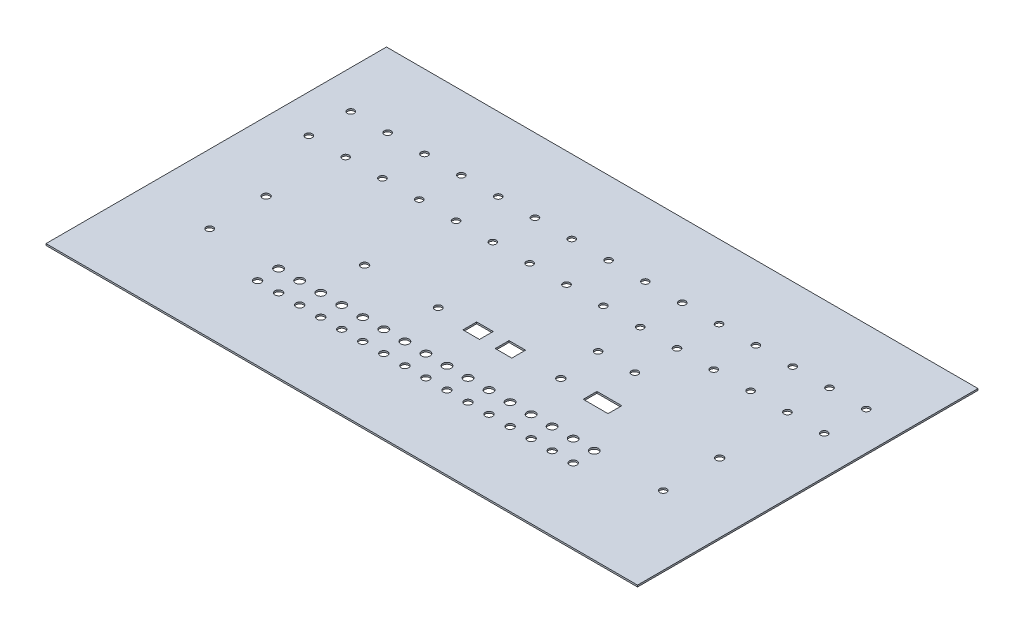
SolidWorks part; units mm, degrees
ref_plane "Front Plane" through (0, 0, 0) normal (0, 0, 1) x (1, 0, 0)
ref_plane "Top Plane" through (0, 0, 0) normal (0, 1, 0) x (1, 0, 0)
ref_plane "Right Plane" through (0, 0, 0) normal (1, 0, 0) x (0, 0, -1)
sketch "Sketch1" plane through (0, 0, 0) normal (0, 1, 0) x (1, 0, 0)
  line L1 (281.15, -161.825) -> (-281.15, -161.825)
  line L2 (281.15, -161.825) -> (281.15, 161.825)
  line L3 (281.15, 161.825) -> (-281.15, 161.825)
  line L4 (-281.15, -161.825) -> (-281.15, 161.825)
  line L5 (281.15, -161.825) -> (-281.15, 161.825) construction
  line L6 (281.15, 161.825) -> (-281.15, -161.825) construction
  point P0 (0, 0)
  dimension "D1" = 323.65
  dimension "D2" = 562.3
extrude "Boss-Extrude1" add sketch "Sketch1" along normal blind 1.5875
sketch "Sketch2" plane through (0, 1.5875, 0) normal (0, 1, 0) x (1, 0, 0)
  line L0 (-281.15, 161.825) -> (-281.15, -161.825) construction
  line L1 (281.15, 161.825) -> (-281.15, 161.825) construction
  circle A0 centre (-245, 91.825) radius 3.25
  dimension "D1" = 6.5
  dimension "D2" = 36.15
  dimension "D3" = 70
extrude "Cut-Extrude1" cut sketch "Sketch2" against normal up to next
sketch "Sketch3" plane through (0, 1.5875, 0) normal (0, 1, 0) x (1, 0, 0)
  circle A0 centre (-245, 91.825) radius 9.5
pattern_linear "LPattern1" count 15 spacing 35 along (1, 0, 0) count 2 spacing 40 along (0, 0, 1) of "Cut-Extrude1"
sketch "Sketch6" plane through (0, 1.5875, 0) normal (0, 1, 0) x (1, 0, 0)
  line L0 (-281.15, 161.825) -> (-281.15, -161.825) construction
  line L1 (-281.15, -161.825) -> (281.15, -161.825) construction
  circle A0 centre (-150, -91.825) radius 3.5
  dimension "D1" = 131.15
  dimension "D2" = 70
extrude "Cut-Extrude2" cut sketch "Sketch6" against normal up to next
pattern_linear "LPattern2" count 16 spacing 20 along (1, 0, 0) of "Cut-Extrude2"
sketch "Sketch7" plane through (0, 1.5875, 0) normal (0, 1, 0) x (1, 0, 0)
  line L0 (-281.15, 161.825) -> (-281.15, -161.825) construction
  circle A0 centre (-150, -71.825) radius 4
  circle A1 centre (-150, -91.825) radius 3.5 construction
  dimension "D1" = 131.15
  dimension "D2" = 20
extrude "Cut-Extrude3" cut sketch "Sketch7" against normal up to next
pattern_linear "LPattern3" count 16 spacing 20 along (1, 0, 0) of "Cut-Extrude3"
sketch "Sketch8" plane through (0, 1.5875, 0) normal (0, 1, 0) x (1, 0, 0)
  line L1 (-281.15, 161.825) -> (-281.15, -161.825) construction
  line L2 (-281.15, -161.825) -> (281.15, -161.825) construction
  circle A0 centre (-215.575, -71.825) radius 3.3
  dimension "D1" = 90
  dimension "D2" = 65.575
extrude "Cut-Extrude4" cut sketch "Sketch8" against normal up to next
sketch "Sketch10" plane through (0, 1.5875, 0) normal (0, 1, 0) x (1, 0, 0)
  line L0 (281.15, -161.825) -> (281.15, 161.825) construction
  line L1 (-281.15, -161.825) -> (281.15, -161.825) construction
  circle A0 centre (215.575, -71.825) radius 3.25
  dimension "D1" = 65.575
  dimension "D2" = 90
extrude "Cut-Extrude5" cut sketch "Sketch10" against normal up to next
sketch "Sketch11" plane through (0, 1.5875, 0) normal (0, 1, 0) x (1, 0, 0)
  line L0 (281.15, 161.825) -> (-281.15, 161.825) construction
  circle A0 centre (74.5943, -28.175) radius 3.5
  dimension "D1" = 190
  dimension "D2" = 7
extrude "Cut-Extrude6" cut sketch "Sketch11" against normal up to next
sketch "Sketch12" plane through (0, 1.5875, 0) normal (0, 1, 0) x (1, 0, 0)
  text T0 "BPM Control\r\n\r\n"
sketch "Sketch13" plane through (0, 1.5875, 0) normal (0, 1, 0) x (1, 0, 0)
  text T0 "Channel Select"
sketch "Sketch14" plane through (0, 1.5875, 0) normal (0, 1, 0) x (1, 0, 0)
  text T0 "Master Volume\r\n"
sketch "Sketch15" plane through (0, 1.5875, 0) normal (0, 1, 0) x (1, 0, 0)
  line L0 (281.15, 161.825) -> (-281.15, 161.825) construction
  line L1 (126.0074, -34.715) -> (102.3974, -34.715)
  line L2 (126.0074, -34.715) -> (126.0074, -21.635)
  line L3 (126.0074, -21.635) -> (102.3974, -21.635)
  line L4 (102.3974, -34.715) -> (102.3974, -21.635)
  line L5 (126.0074, -34.715) -> (102.3974, -21.635) construction
  line L6 (126.0074, -21.635) -> (102.3974, -34.715) construction
  point P0 (114.2024, -28.175)
  dimension "D1" = 13.08
  dimension "D2" = 23.61
  dimension "D3" = 190
extrude "Cut-Extrude7" cut sketch "Sketch15" against normal up to next
sketch "Sketch16" plane through (0, 1.5875, 0) normal (0, 1, 0) x (1, 0, 0)
  line L0 (281.15, 161.825) -> (-281.15, 161.825) construction
  circle A0 centre (-41.9525, -28.175) radius 3.3
  dimension "D1" = 190
extrude "Cut-Extrude8" cut sketch "Sketch16" against normal up to next contours A0
sketch "Sketch17" plane through (0, 1.5875, 0) normal (0, 1, 0) x (1, 0, 0)
  text T0 "Loop Back Control\r\n"
sketch "Sketch18" plane through (0, 1.5875, 0) normal (0, 1, 0) x (1, 0, 0)
  line L0 (102.3974, -34.715) -> (126.0074, -34.715) construction
  line L1 (3.7875, -34.715) -> (-11.9525, -34.715)
  line L2 (3.7875, -34.715) -> (3.7875, -21.635)
  line L3 (3.7875, -21.635) -> (-11.9525, -21.635)
  line L4 (-11.9525, -34.715) -> (-11.9525, -21.635)
  line L5 (3.7875, -34.715) -> (-11.9525, -21.635) construction
  line L6 (3.7875, -21.635) -> (-11.9525, -34.715) construction
  point P0 (-4.0825, -28.175)
  dimension "D1" = 13.08
  dimension "D2" = 15.74
  dimension "D3" = 0
extrude "Cut-Extrude9" cut sketch "Sketch18" against normal up to next
sketch "Sketch19" plane through (0, 1.5875, 0) normal (0, 1, 0) x (1, 0, 0)
  line L1 (34.5275, -34.715) -> (18.7875, -34.715)
  line L2 (34.5275, -34.715) -> (34.5275, -21.635)
  line L3 (34.5275, -21.635) -> (18.7875, -21.635)
  line L4 (18.7875, -34.715) -> (18.7875, -21.635)
  line L5 (34.5275, -34.715) -> (18.7875, -21.635) construction
  line L6 (34.5275, -21.635) -> (18.7875, -34.715) construction
  line L7 (-11.9525, -34.715) -> (3.7875, -34.715) construction
  line L8 (3.7875, -34.715) -> (3.7875, -21.635) construction
  point P0 (26.6575, -28.175)
  dimension "D4" = 15
  dimension "D1" = 13.08
  dimension "D2" = 15.74
  dimension "D3" = 0
extrude "Cut-Extrude10" cut sketch "Sketch19" against normal up to next
sketch "Sketch20" plane through (0, 1.5875, 0) normal (0, 1, 0) x (1, 0, 0)
  text T0 "Loop Back"
sketch "Sketch21" plane through (0, 1.5875, 0) normal (0, 1, 0) x (1, 0, 0)
  text T0 "Current Position"
sketch "Sketch22" plane through (0, 1.5875, 0) normal (0, 1, 0) x (1, 0, 0)
  line L0 (281.15, 161.825) -> (-281.15, 161.825) construction
  circle A0 centre (-111.9525, -28.175) radius 3.5
  circle A2 centre (-41.9525, -28.175) radius 3.3 construction
  dimension "D1" = 190
  dimension "D2" = 70
  dimension "D3" = 7
extrude "Cut-Extrude11" cut sketch "Sketch22" against normal up to next
sketch "Sketch23" plane through (0, 1.5875, 0) normal (0, 1, 0) x (1, 0, 0)
  text T0 "Measure Select"
sketch "Sketch24" plane through (0, 1.5875, 0) normal (0, 1, 0) x (1, 0, 0)
  line L0 (-281.15, 161.825) -> (-281.15, -161.825) construction
  line L1 (281.15, 161.825) -> (-281.15, 161.825) construction
  circle A0 centre (-215.57, -18.175) radius 3.5
  text T0 "Start/Stop"
  dimension "D1" = 65.58
  dimension "D2" = 180
extrude "Cut-Extrude12" cut sketch "Sketch24" against normal up to next contours A0
sketch "Sketch25" plane through (0, 1.5875, 0) normal (0, 1, 0) x (1, 0, 0)
  text T0 "Start/Stop\r\n"
sketch "Sketch26" plane through (0, 1.5875, 0) normal (0, 1, 0) x (1, 0, 0)
  line L0 (281.15, -161.825) -> (281.15, 161.825) construction
  line L1 (281.15, 161.825) -> (-281.15, 161.825) construction
  circle A0 centre (215.57, -18.175) radius 3.5
  dimension "D1" = 65.58
  dimension "D2" = 180
extrude "Cut-Extrude13" cut sketch "Sketch26" against normal up to next
sketch "Sketch27" plane through (0, 1.5875, 0) normal (0, 1, 0) x (1, 0, 0)
  text T0 "Reset"
sketch "Sketch28" plane through (0, 1.5875, 0) normal (0, 1, 0) x (1, 0, 0)
  line L0 (281.15, -161.825) -> (281.15, 161.825) construction
  circle A0 centre (70, 11.825) radius 3.25
  circle A1 centre (70, 51.825) radius 3.25 construction
  dimension "D1" = 40
  dimension "D2" = 211.15
extrude "Cut-Extrude14" cut sketch "Sketch28" against normal up to next
sketch "Sketch29" plane through (0, 1.5875, 0) normal (0, 1, 0) x (1, 0, 0)
  circle A0 centre (105, 11.825) radius 3.25
  circle A1 centre (70, 11.825) radius 3.25 construction
  circle A2 centre (105, 51.825) radius 3.25 construction
  dimension "D1" = 35
  dimension "D2" = 40
extrude "Cut-Extrude15" cut sketch "Sketch29" against normal up to next
